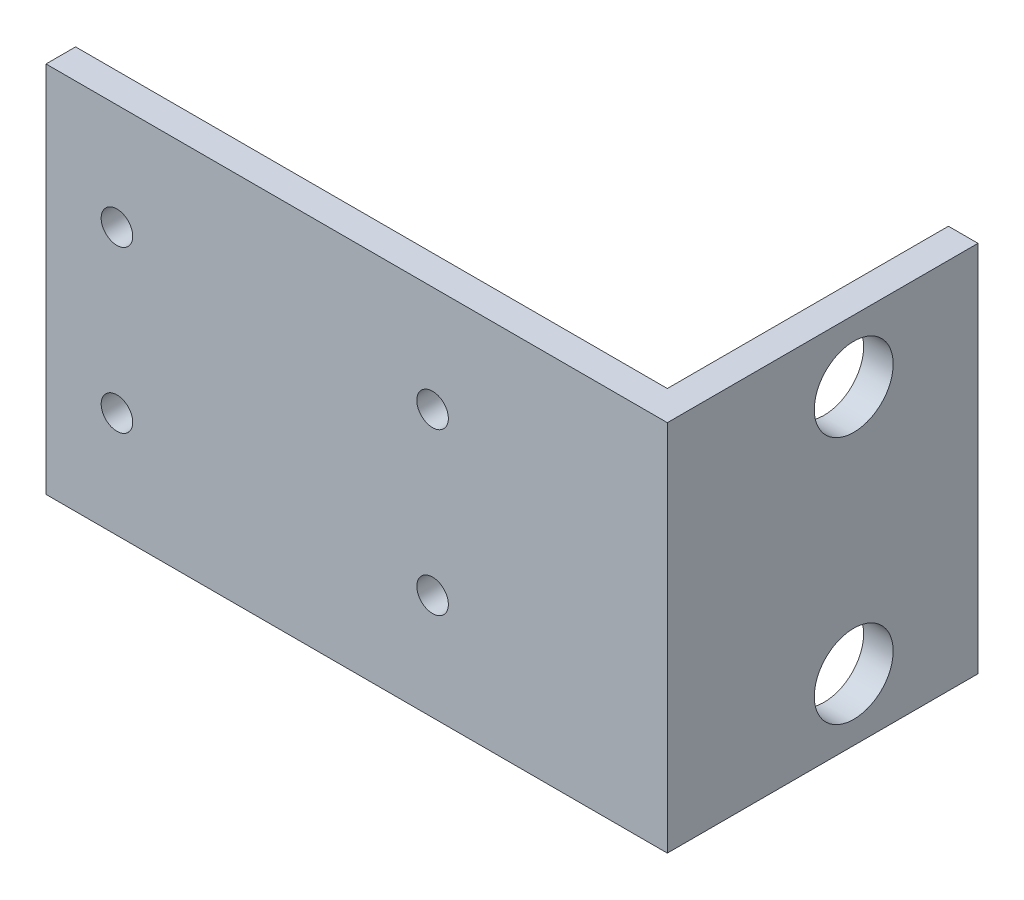
SolidWorks part; units mm, degrees
ref_plane "Front Plane" through (0, 0, 0) normal (0, 0, 1) x (1, 0, 0)
ref_plane "Top Plane" through (0, 0, 0) normal (0, 1, 0) x (1, 0, 0)
ref_plane "Right Plane" through (0, 0, 0) normal (1, 0, 0) x (0, 0, -1)
sketch "Sketch1" plane through (0, 0, 0) normal (0, 1, 0) x (1, 0, 0)
  line L0 (0, 0) -> (0, 22.6188)
  line L1 (0, 22.6188) -> (2.3813, 22.6188)
  line L2 (2.3813, 22.6188) -> (2.3813, -2.3812)
  line L3 (2.3813, -2.3812) -> (-47.6187, -2.3813)
  line L4 (-47.6187, -2.3813) -> (-47.6187, 0)
  line L5 (-47.6187, 0) -> (0, 0)
  dimension "D1" = 2.3813
  dimension "D2" = 25
  dimension "D3" = 50
extrude "Boss-Extrude1" add sketch "Sketch1" along normal blind 30
sketch "Sketch2" plane through (0, 0, 2.3812) normal (0, 0, 1) x (1, 0, 0)
  line L4 (-47.6187, 0) -> (2.3813, 0)
  line L5 (2.3813, 0) -> (2.3813, 30)
  line L6 (2.3813, 30) -> (-47.6187, 30)
  line L7 (-47.6187, 30) -> (-47.6187, 0)
  line L8 (-47.6187, 0) -> (2.3813, 0) construction
  line L9 (2.3813, 0) -> (2.3813, 30) construction
  line L10 (2.3813, 30) -> (-47.6187, 30) construction
  line L11 (-47.6187, 30) -> (-47.6187, 0) construction
  circle A0 centre (-41.91, 8.523) radius 1.27 construction
  circle A1 centre (-41.91, 8.523) radius 1.27
  circle A2 centre (-16.51, 8.523) radius 1.27 construction
  circle A3 centre (-16.51, 8.523) radius 1.27
  circle A4 centre (-16.51, 21.477) radius 1.27 construction
  circle A5 centre (-16.51, 21.477) radius 1.27
  circle A6 centre (-41.91, 21.477) radius 1.27 construction
  circle A7 centre (-41.91, 21.477) radius 1.27
  dimension "D1" = 0
extrude "Cut-Extrude1" cut sketch "Sketch2" against normal through all
sketch "Sketch3" plane through (2.3813, 0, 0) normal (1, 0, 0) x (0, 0, -1)
  line L4 (-2.3812, 0) -> (22.6188, 0)
  line L5 (22.6188, 0) -> (22.6188, 30)
  line L6 (22.6188, 30) -> (-2.3812, 30)
  line L7 (-2.3812, 30) -> (-2.3812, 0)
  line L8 (-2.3812, 0) -> (22.6188, 0) construction
  line L9 (22.6188, 0) -> (22.6188, 30) construction
  line L10 (22.6188, 30) -> (-2.3812, 30) construction
  line L11 (-2.3812, 30) -> (-2.3812, 0) construction
  circle A0 centre (12.6188, 25) radius 3.175
  circle A1 centre (12.6188, 5) radius 3.175
  point P2 (12.6188, 25)
  point P4 (12.6188, 5)
  dimension "D5" = 6.35
  dimension "D2" = 20
  dimension "D3" = 5
  dimension "D4" = 15
  dimension "D1" = 0
extrude "Cut-Extrude2" cut sketch "Sketch3" against normal through all
